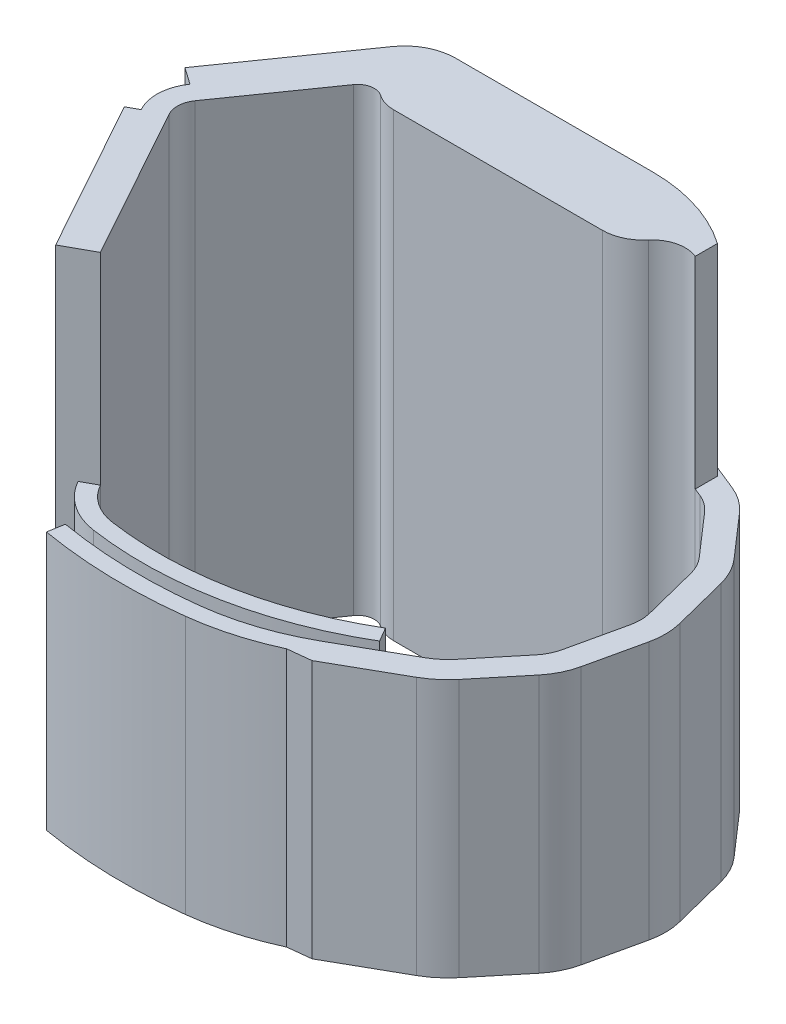
SolidWorks part; units mm, degrees
ref_plane "Front Plane" through (0, 0, 0) normal (0, 0, 1) x (1, 0, 0)
ref_plane "Top Plane" through (0, 0, 0) normal (0, 1, 0) x (1, 0, 0)
ref_plane "Right Plane" through (0, 0, 0) normal (1, 0, 0) x (0, 0, -1)
sketch "Sketch1" plane through (0, 0, 0) normal (0, 1, 0) x (1, 0, 0)
  line L25 (0, 0) -> (30, 0)
  line L26 (0, 0) -> (0, 5.1)
  line L27 (0, 5.1) -> (-11.3568, -11.1192)
  line L28 (-11.5142, -14.1151) -> (-1.1434, -32.8343)
  line L29 (30, 0) -> (30, 5.1)
  line L30 (30, 5.1) -> (36.396, 2.5112)
  line L31 (38.3662, 1.1076) -> (42.9025, -4.0916)
  line L32 (44.0261, -6.234) -> (45.7239, -12.9219)
  line L33 (45.7583, -15.3407) -> (44.2512, -22.0741)
  line L34 (43.189, -24.2476) -> (38.8023, -29.5737)
  line L35 (36.8101, -31.2464) -> (28.7168, -35.8276)
  line L36 (43.189, -24.2476) -> (44.2512, -22.0741) construction
  line L37 (45.7583, -15.3407) -> (45.7239, -12.9219) construction
  line L38 (44.0261, -6.234) -> (42.9025, -4.0916) construction
  line L39 (38.3662, 1.1076) -> (36.396, 2.5112) construction
  line L40 (37.7953, -32.9869) -> (29.702, -37.5682) construction
  line L41 (44.7328, -25.5191) -> (40.3461, -30.8452) construction
  line L42 (47.71, -15.7775) -> (46.2029, -22.511) construction
  line L43 (45.9646, -5.7419) -> (47.6624, -12.4297) construction
  line L44 (39.8733, 2.4225) -> (44.4096, -2.7768) construction
  line L45 (28, 8.0671) -> (37.1463, 4.3651) construction
  line L46 (0.8423, -39.0787) -> (0.5054, -41.0501)
  line L47 (32.2441, -32.2796) -> (31.228, -30.5569)
  line L48 (-1.1434, -32.8343) -> (-4.6424, -34.7727) construction
  line L49 (-4.6424, -34.7727) -> (-15.0131, -16.0535)
  line L50 (-4.6424, -34.7727) -> (-2.8929, -33.8035)
  line L51 (2, 2) -> (2, 11.4432) construction
  line L52 (2, 2) -> (28, 2) construction
  line L53 (28, 2) -> (28, 8.0671) construction
  line L54 (-13.2636, -15.0843) -> (-2.8929, -33.8035) construction
  line L55 (2, 11.4432) -> (-12.9951, -9.9721) construction
  line L56 (-13.701, -15.3266) -> (-15.0131, -16.0535)
  line L57 (-13.4047, -9.6853) -> (-15.4526, -8.2513)
  line L58 (-15.4526, -8.2513) -> (-5.0874, 6.5517)
  line L59 (23.9723, 9.2) -> (0, 9.2)
  line L60 (31.476, 7.739) -> (37.5215, 5.2921)
  line L61 (40.6268, 3.0799) -> (45.1631, -2.1193)
  line L62 (46.9338, -5.4958) -> (48.6316, -12.1837)
  line L63 (48.6858, -15.996) -> (47.1788, -22.7294)
  line L64 (45.5047, -26.1548) -> (41.118, -31.4809)
  line L65 (38.2879, -33.8572) -> (30.1946, -38.4384)
  line L66 (30.1946, -38.4384) -> (27.4052, -38.748)
  line L67 (31.1256, 7.8809) -> (37.5215, 5.2921) construction
  arc A0 (-11.3568, -11.1192) -> (-11.5142, -14.1151) centre (-9.0377, -12.7431) ccw
  arc A1 (-1.1434, -32.8343) -> (3.45, -36.0108) centre (4.3601, -29.7852) ccw
  arc A2 (36.396, 2.5112) -> (38.3662, 1.1076) centre (34.4421, -2.3162) cw
  arc A3 (42.9025, -4.0916) -> (44.0261, -6.234) centre (38.9783, -7.5154) cw
  arc A4 (45.7239, -12.9219) -> (45.7583, -15.3407) centre (40.6761, -14.2033) cw
  arc A5 (44.2512, -22.0741) -> (43.189, -24.2476) centre (39.1691, -20.9367) cw
  arc A6 (38.8023, -29.5737) -> (36.8101, -31.2464) centre (33.2962, -25.0387) cw
  arc A7 (28.7168, -35.8276) -> (17.6013, -39.4854) centre (14.0041, -9.8357) cw
  arc A8 (3.45, -36.0108) -> (31.228, -30.5569) centre (9.6063, 6.1007) ccw
  arc A9 (17.6013, -39.4854) -> (0.8423, -39.0787) centre (10.6143, 18.1035) cw
  arc A10 (17.8422, -41.4708) -> (0.5054, -41.0501) centre (10.6143, 18.1035) cw
  arc A11 (29.702, -37.5682) -> (17.8422, -41.4708) centre (14.0041, -9.8357) cw construction
  arc A12 (40.3461, -30.8452) -> (37.7953, -32.9869) centre (33.2962, -25.0387) cw construction
  arc A13 (46.2029, -22.511) -> (44.7328, -25.5191) centre (39.1691, -20.9367) cw construction
  arc A14 (47.6624, -12.4297) -> (47.71, -15.7775) centre (40.6761, -14.2033) cw construction
  arc A15 (44.4096, -2.7768) -> (45.9646, -5.7419) centre (38.9783, -7.5154) cw construction
  arc A16 (37.1463, 4.3651) -> (39.8733, 2.4225) centre (34.4421, -2.3162) cw construction
  arc A17 (-13.701, -15.3266) -> (-13.4047, -9.6853) centre (-9.0377, -12.7431) cw
  arc A18 (-2.8929, -33.8035) -> (3.1607, -37.9898) centre (4.3601, -29.7852) ccw
  arc A19 (3.1607, -37.9898) -> (32.2441, -32.2796) centre (9.6063, 6.1007) ccw
  arc A20 (-12.9951, -9.9721) -> (-13.2636, -15.0843) centre (-9.0377, -12.7431) ccw construction
  arc A21 (-5.0874, 6.5517) -> (0, 9.2) centre (0, 2.9894) cw
  arc A22 (37.5215, 5.2921) -> (40.6268, 3.0799) centre (34.4421, -2.3162) cw
  arc A23 (45.1631, -2.1193) -> (46.9338, -5.4958) centre (38.9783, -7.5154) cw
  arc A24 (48.6316, -12.1837) -> (48.6858, -15.996) centre (40.6761, -14.2033) cw
  arc A25 (47.1788, -22.7294) -> (45.5047, -26.1548) centre (39.1691, -20.9367) cw
  arc A26 (41.118, -31.4809) -> (38.2879, -33.8572) centre (33.2962, -25.0387) cw
  arc A27 (23.9723, 9.2) -> (31.476, 7.739) centre (23.9723, -10.8) cw
  arc A28 (17.8422, -41.4708) -> (27.4052, -38.748) centre (14.0041, -9.8357) ccw
  dimension "D8" = 6.9
  dimension "D11" = 2.5
  dimension "D16" = 20
  dimension "D1" = 5.1
  dimension "D2" = 30
  dimension "D3" = 19.8
  dimension "D4" = 21.4
  dimension "D5" = 3
  dimension "D6" = 6.9
  dimension "D7" = 9.3
  dimension "D9" = 2
  dimension "D10" = 4
  dimension "D12" = 5
  dimension "D13" = 67.964
  dimension "D14" = 9.2
  dimension "D15" = 3
extrude "Boss-Extrude1" add sketch "Sketch1" along normal blind 23.4 contours L58 A21 L59 A27 L60 A22 L61 A23 L62 A24 L63 A25 L64 A26 L65 L66 A28 A10 L46 A9 A7 L35 A6 L34 A5 L33 A4 L32 A3 L31 A2 L30 L29 L25 L26 L27 A0 L28 A1 A8 L47 A19 A18 L50 L49 L56 A17 L57
fillet "Fillet1" radius 4 1 edges at (30, 11.7, -5.1)
fillet "Fillet3" radius 2 1 edges at (0, 11.7, -5.1)
fillet "Fillet4" radius 4 1 edges at (0, 11.7, 0)
fillet "Fillet5" radius 5 1 edges at (30, 11.7, 0)
sketch "Sketch2" plane through (0, 23.4, 0) normal (0, 1, 0) x (1, 0, 0)
  line L0 (-2.8929, -33.8035) -> (-1.1434, -32.8343)
  line L1 (35.4196, 2.9064) -> (35.4196, 5.6)
  line L26 (-15.4526, -8.2513) -> (-13.4047, -9.6853)
  line L27 (-13.701, -15.3266) -> (-15.0131, -16.0535)
  line L28 (-15.0131, -16.0535) -> (-4.6424, -34.7727)
  line L29 (-4.6424, -34.7727) -> (-2.8929, -33.8035)
  line L30 (32.2441, -32.2796) -> (31.228, -30.5569)
  line L31 (-1.1434, -32.8343) -> (-11.5142, -14.1151)
  line L32 (-11.3568, -11.1192) -> (-3.4132, 0.2254)
  line L34 (1.6567, 0) -> (27.0382, 0)
  line L36 (35.4196, 2.9064) -> (36.396, 2.5112)
  line L37 (38.3662, 1.1076) -> (42.9025, -4.0916)
  line L38 (44.0261, -6.234) -> (45.7239, -12.9219)
  line L39 (45.7583, -15.3407) -> (44.2512, -22.0741)
  line L40 (43.189, -24.2476) -> (38.8023, -29.5737)
  line L41 (36.8101, -31.2464) -> (28.7168, -35.8276)
  line L42 (0.8423, -39.0787) -> (0.5054, -41.0501)
  line L43 (27.4052, -38.748) -> (30.1946, -38.4384)
  line L44 (30.1946, -38.4384) -> (38.2879, -33.8572)
  line L45 (41.118, -31.4809) -> (45.5047, -26.1548)
  line L46 (47.1788, -22.7294) -> (48.6858, -15.996)
  line L47 (48.6316, -12.1837) -> (46.9338, -5.4958)
  line L48 (45.1631, -2.1193) -> (40.6268, 3.0799)
  line L49 (37.5215, 5.2921) -> (31.476, 7.739)
  line L50 (23.9723, 9.2) -> (0, 9.2)
  line L51 (-5.0874, 6.5517) -> (-15.4526, -8.2513)
  line L52 (-15.4526, -8.2513) -> (-13.4047, -9.6853)
  line L53 (-13.701, -15.3266) -> (-15.0131, -16.0535)
  line L54 (-15.0131, -16.0535) -> (-4.6424, -34.7727)
  line L55 (-4.6424, -34.7727) -> (-2.8929, -33.8035)
  line L57 (-1.1434, -32.8343) -> (-11.5142, -14.1151)
  line L58 (-11.3568, -11.1192) -> (-3.4132, 0.2254)
  line L60 (1.6567, 0) -> (27.0382, 0)
  line L76 (23.9723, 9.2) -> (0, 9.2)
  line L77 (-5.0874, 6.5517) -> (-15.4526, -8.2513)
  arc A22 (-13.4047, -9.6853) -> (-13.701, -15.3266) centre (-9.0377, -12.7431) ccw
  arc A23 (-2.8929, -33.8035) -> (3.1607, -37.9898) centre (4.3601, -29.7852) ccw
  arc A24 (3.1607, -37.9898) -> (32.2441, -32.2796) centre (9.6063, 6.1007) ccw
  arc A25 (3.45, -36.0108) -> (31.228, -30.5569) centre (9.6063, 6.1007) ccw
  arc A26 (-1.1434, -32.8343) -> (3.45, -36.0108) centre (4.3601, -29.7852) ccw
  arc A27 (-11.3568, -11.1192) -> (-11.5142, -14.1151) centre (-9.0377, -12.7431) ccw
  arc A28 (38.3662, 1.1076) -> (36.396, 2.5112) centre (34.4421, -2.3162) ccw
  arc A29 (44.0261, -6.234) -> (42.9025, -4.0916) centre (38.9783, -7.5154) ccw
  arc A30 (45.7583, -15.3407) -> (45.7239, -12.9219) centre (40.6761, -14.2033) ccw
  arc A31 (43.189, -24.2476) -> (44.2512, -22.0741) centre (39.1691, -20.9367) ccw
  arc A32 (36.8101, -31.2464) -> (38.8023, -29.5737) centre (33.2962, -25.0387) ccw
  arc A33 (17.6013, -39.4854) -> (28.7168, -35.8276) centre (14.0041, -9.8357) ccw
  arc A34 (0.8423, -39.0787) -> (17.6013, -39.4854) centre (10.6143, 18.1035) ccw
  arc A35 (0.5054, -41.0501) -> (17.8422, -41.4708) centre (10.6143, 18.1035) ccw
  arc A36 (17.8422, -41.4708) -> (27.4052, -38.748) centre (14.0041, -9.8357) ccw
  arc A37 (38.2879, -33.8572) -> (41.118, -31.4809) centre (33.2962, -25.0387) ccw
  arc A38 (45.5047, -26.1548) -> (47.1788, -22.7294) centre (39.1691, -20.9367) ccw
  arc A39 (48.6858, -15.996) -> (48.6316, -12.1837) centre (40.6761, -14.2033) ccw
  arc A40 (46.9338, -5.4958) -> (45.1631, -2.1193) centre (38.9783, -7.5154) ccw
  arc A41 (40.6268, 3.0799) -> (37.5215, 5.2921) centre (34.4421, -2.3162) ccw
  arc A42 (31.476, 7.739) -> (23.9723, 9.2) centre (23.9723, -10.8) ccw
  arc A43 (0, 9.2) -> (-5.0874, 6.5517) centre (0, 2.9894) ccw
  arc A44 (-13.4047, -9.6853) -> (-13.701, -15.3266) centre (-9.0377, -12.7431) ccw
  arc A49 (-11.3568, -11.1192) -> (-11.5142, -14.1151) centre (-9.0377, -12.7431) ccw
  arc A51 (44.0261, -6.234) -> (42.9025, -4.0916) centre (38.9783, -7.5154) ccw
  arc A54 (36.8101, -31.2464) -> (38.8023, -29.5737) centre (33.2962, -25.0387) ccw
  arc A64 (35.4196, 5.6) -> (23.9723, 9.2) centre (23.9723, -10.8) ccw
  arc A65 (0, 9.2) -> (-5.0874, 6.5517) centre (0, 2.9894) ccw
  arc A70 (27.0382, 0) -> (30.8608, 1.777) centre (27.0382, 5) ccw
  arc A71 (27.0382, 0) -> (30.8608, 1.777) centre (27.0382, 5) ccw
  arc A72 (35.4196, 2.9064) -> (30.8608, 1.777) centre (33.9189, -0.8014) ccw
  arc A73 (35.4196, 2.9064) -> (30.8608, 1.777) centre (33.9189, -0.8014) ccw
  arc A74 (-0.631, 0.7188) -> (-3.4132, 0.2254) centre (-1.7749, -0.9218) ccw
  arc A75 (-0.631, 0.7188) -> (-3.4132, 0.2254) centre (-1.7749, -0.9218) ccw
  arc A76 (-0.631, 0.7188) -> (1.6567, 0) centre (1.6567, 4) ccw
  arc A77 (-0.631, 0.7188) -> (1.6567, 0) centre (1.6567, 4) ccw
  dimension "D1" = 0
extrude "Boss-Extrude2" add sketch "Sketch2" along normal blind 24.5
sketch "Sketch3" plane through (0, 0, 0) normal (0, -1, 0) x (1, 0, 0)
  line L24 (27.0382, 0) -> (1.6567, 0)
  line L25 (-3.4132, -0.2254) -> (-11.3568, 11.1192)
  line L26 (-11.5142, 14.1151) -> (-1.1434, 32.8343)
  line L27 (31.228, 30.5569) -> (32.2441, 32.2796)
  line L28 (-2.8929, 33.8035) -> (-4.6424, 34.7727)
  line L29 (-4.6424, 34.7727) -> (-15.0131, 16.0535)
  line L30 (-15.0131, 16.0535) -> (-13.701, 15.3266)
  line L31 (-13.4047, 9.6853) -> (-15.4526, 8.2513)
  line L32 (-15.4526, 8.2513) -> (-5.0874, -6.5517)
  line L33 (0, -9.2) -> (23.9723, -9.2)
  line L34 (31.476, -7.739) -> (37.5215, -5.2921)
  line L35 (40.6268, -3.0799) -> (45.1631, 2.1193)
  line L36 (46.9338, 5.4958) -> (48.6316, 12.1837)
  line L37 (48.6858, 15.996) -> (47.1788, 22.7294)
  line L38 (45.5047, 26.1548) -> (41.118, 31.4809)
  line L39 (38.2879, 33.8572) -> (30.1946, 38.4384)
  line L40 (30.1946, 38.4384) -> (27.4052, 38.748)
  line L41 (0.5054, 41.0501) -> (0.8423, 39.0787)
  line L42 (28.7168, 35.8276) -> (36.8101, 31.2464)
  line L43 (38.8023, 29.5737) -> (43.189, 24.2476)
  line L44 (44.2512, 22.0741) -> (45.7583, 15.3407)
  line L45 (45.7239, 12.9219) -> (44.0261, 6.234)
  line L46 (42.9025, 4.0916) -> (38.3662, -1.1076)
  line L47 (36.396, -2.5112) -> (35.4196, -2.9064)
  line L48 (27.0382, 0) -> (1.6567, 0)
  line L49 (-3.4132, -0.2254) -> (-11.3568, 11.1192)
  line L50 (-11.5142, 14.1151) -> (-1.1434, 32.8343)
  line L51 (31.228, 30.5569) -> (32.2441, 32.2796)
  line L52 (-2.8929, 33.8035) -> (-4.6424, 34.7727)
  line L53 (-4.6424, 34.7727) -> (-15.0131, 16.0535)
  line L54 (-15.0131, 16.0535) -> (-13.701, 15.3266)
  line L55 (-13.4047, 9.6853) -> (-15.4526, 8.2513)
  line L56 (-15.4526, 8.2513) -> (-5.0874, -6.5517)
  line L57 (0, -9.2) -> (23.9723, -9.2)
  line L58 (31.476, -7.739) -> (37.5215, -5.2921)
  line L59 (40.6268, -3.0799) -> (45.1631, 2.1193)
  line L60 (46.9338, 5.4958) -> (48.6316, 12.1837)
  line L61 (48.6858, 15.996) -> (47.1788, 22.7294)
  line L62 (45.5047, 26.1548) -> (41.118, 31.4809)
  line L63 (38.2879, 33.8572) -> (30.1946, 38.4384)
  line L64 (30.1946, 38.4384) -> (27.4052, 38.748)
  line L65 (0.5054, 41.0501) -> (0.8423, 39.0787)
  line L66 (28.7168, 35.8276) -> (36.8101, 31.2464)
  line L67 (38.8023, 29.5737) -> (43.189, 24.2476)
  line L68 (44.2512, 22.0741) -> (45.7583, 15.3407)
  line L69 (45.7239, 12.9219) -> (44.0261, 6.234)
  line L70 (42.9025, 4.0916) -> (38.3662, -1.1076)
  line L71 (36.396, -2.5112) -> (35.4196, -2.9064)
  circle A0 centre (-4.3104, 30.7092) radius 0.75
  circle A1 centre (32.1116, 35.6124) radius 0.75
  circle A2 centre (14.0041, -5.2921) radius 0.75
  arc A26 (30.8608, -1.777) -> (35.4196, -2.9064) centre (33.9189, 0.8014) ccw
  arc A27 (30.8608, -1.777) -> (27.0382, 0) centre (27.0382, -5) ccw
  arc A28 (1.6567, 0) -> (-0.631, -0.7188) centre (1.6567, -4) ccw
  arc A29 (-3.4132, -0.2254) -> (-0.631, -0.7188) centre (-1.7749, 0.9218) ccw
  arc A30 (-11.5142, 14.1151) -> (-11.3568, 11.1192) centre (-9.0377, 12.7431) ccw
  arc A31 (3.45, 36.0108) -> (-1.1434, 32.8343) centre (4.3601, 29.7852) ccw
  arc A32 (31.228, 30.5569) -> (3.45, 36.0108) centre (9.6063, -6.1007) ccw
  arc A33 (32.2441, 32.2796) -> (3.1607, 37.9898) centre (9.6063, -6.1007) ccw
  arc A34 (3.1607, 37.9898) -> (-2.8929, 33.8035) centre (4.3601, 29.7852) ccw
  arc A35 (-13.701, 15.3266) -> (-13.4047, 9.6853) centre (-9.0377, 12.7431) ccw
  arc A36 (-5.0874, -6.5517) -> (0, -9.2) centre (0, -2.9894) ccw
  arc A37 (23.9723, -9.2) -> (31.476, -7.739) centre (23.9723, 10.8) ccw
  arc A38 (37.5215, -5.2921) -> (40.6268, -3.0799) centre (34.4421, 2.3162) ccw
  arc A39 (45.1631, 2.1193) -> (46.9338, 5.4958) centre (38.9783, 7.5154) ccw
  arc A40 (48.6316, 12.1837) -> (48.6858, 15.996) centre (40.6761, 14.2033) ccw
  arc A41 (47.1788, 22.7294) -> (45.5047, 26.1548) centre (39.1691, 20.9367) ccw
  arc A42 (41.118, 31.4809) -> (38.2879, 33.8572) centre (33.2962, 25.0387) ccw
  arc A43 (27.4052, 38.748) -> (17.8422, 41.4708) centre (14.0041, 9.8357) ccw
  arc A44 (17.8422, 41.4708) -> (0.5054, 41.0501) centre (10.6143, -18.1035) ccw
  arc A45 (17.6013, 39.4854) -> (0.8423, 39.0787) centre (10.6143, -18.1035) ccw
  arc A46 (28.7168, 35.8276) -> (17.6013, 39.4854) centre (14.0041, 9.8357) ccw
  arc A47 (38.8023, 29.5737) -> (36.8101, 31.2464) centre (33.2962, 25.0387) ccw
  arc A48 (44.2512, 22.0741) -> (43.189, 24.2476) centre (39.1691, 20.9367) ccw
  arc A49 (45.7239, 12.9219) -> (45.7583, 15.3407) centre (40.6761, 14.2033) ccw
  arc A50 (42.9025, 4.0916) -> (44.0261, 6.234) centre (38.9783, 7.5154) ccw
  arc A51 (36.396, -2.5112) -> (38.3662, -1.1076) centre (34.4421, 2.3162) ccw
  arc A52 (30.8608, -1.777) -> (35.4196, -2.9064) centre (33.9189, 0.8014) ccw
  arc A53 (30.8608, -1.777) -> (27.0382, 0) centre (27.0382, -5) ccw
  arc A54 (1.6567, 0) -> (-0.631, -0.7188) centre (1.6567, -4) ccw
  arc A55 (-3.4132, -0.2254) -> (-0.631, -0.7188) centre (-1.7749, 0.9218) ccw
  arc A56 (-11.5142, 14.1151) -> (-11.3568, 11.1192) centre (-9.0377, 12.7431) ccw
  arc A57 (3.45, 36.0108) -> (-1.1434, 32.8343) centre (4.3601, 29.7852) ccw
  arc A58 (31.228, 30.5569) -> (3.45, 36.0108) centre (9.6063, -6.1007) ccw
  arc A59 (32.2441, 32.2796) -> (3.1607, 37.9898) centre (9.6063, -6.1007) ccw
  arc A60 (3.1607, 37.9898) -> (-2.8929, 33.8035) centre (4.3601, 29.7852) ccw
  arc A61 (-13.701, 15.3266) -> (-13.4047, 9.6853) centre (-9.0377, 12.7431) ccw
  arc A62 (-5.0874, -6.5517) -> (0, -9.2) centre (0, -2.9894) ccw
  arc A63 (23.9723, -9.2) -> (31.476, -7.739) centre (23.9723, 10.8) ccw
  arc A64 (37.5215, -5.2921) -> (40.6268, -3.0799) centre (34.4421, 2.3162) ccw
  arc A65 (45.1631, 2.1193) -> (46.9338, 5.4958) centre (38.9783, 7.5154) ccw
  arc A66 (48.6316, 12.1837) -> (48.6858, 15.996) centre (40.6761, 14.2033) ccw
  arc A67 (47.1788, 22.7294) -> (45.5047, 26.1548) centre (39.1691, 20.9367) ccw
  arc A68 (41.118, 31.4809) -> (38.2879, 33.8572) centre (33.2962, 25.0387) ccw
  arc A69 (27.4052, 38.748) -> (17.8422, 41.4708) centre (14.0041, 9.8357) ccw
  arc A70 (17.8422, 41.4708) -> (0.5054, 41.0501) centre (10.6143, -18.1035) ccw
  arc A71 (17.6013, 39.4854) -> (0.8423, 39.0787) centre (10.6143, -18.1035) ccw
  arc A72 (28.7168, 35.8276) -> (17.6013, 39.4854) centre (14.0041, 9.8357) ccw
  arc A73 (38.8023, 29.5737) -> (36.8101, 31.2464) centre (33.2962, 25.0387) ccw
  arc A74 (44.2512, 22.0741) -> (43.189, 24.2476) centre (39.1691, 20.9367) ccw
  arc A75 (45.7239, 12.9219) -> (45.7583, 15.3407) centre (40.6761, 14.2033) ccw
  arc A76 (42.9025, 4.0916) -> (44.0261, 6.234) centre (38.9783, 7.5154) ccw
  arc A77 (36.396, -2.5112) -> (38.3662, -1.1076) centre (34.4421, 2.3162) ccw
  point P24 (30.1946, 36.0108)
  point P29 (-2.8929, 29.6765)
  point P32 (17.6013, -5)
  point P41 (14.0041, -5.2921)
  dimension "D2" = 1.5
  dimension "D1" = 0
extrude "Boss-Extrude3" add sketch "Sketch3" along normal blind 8
